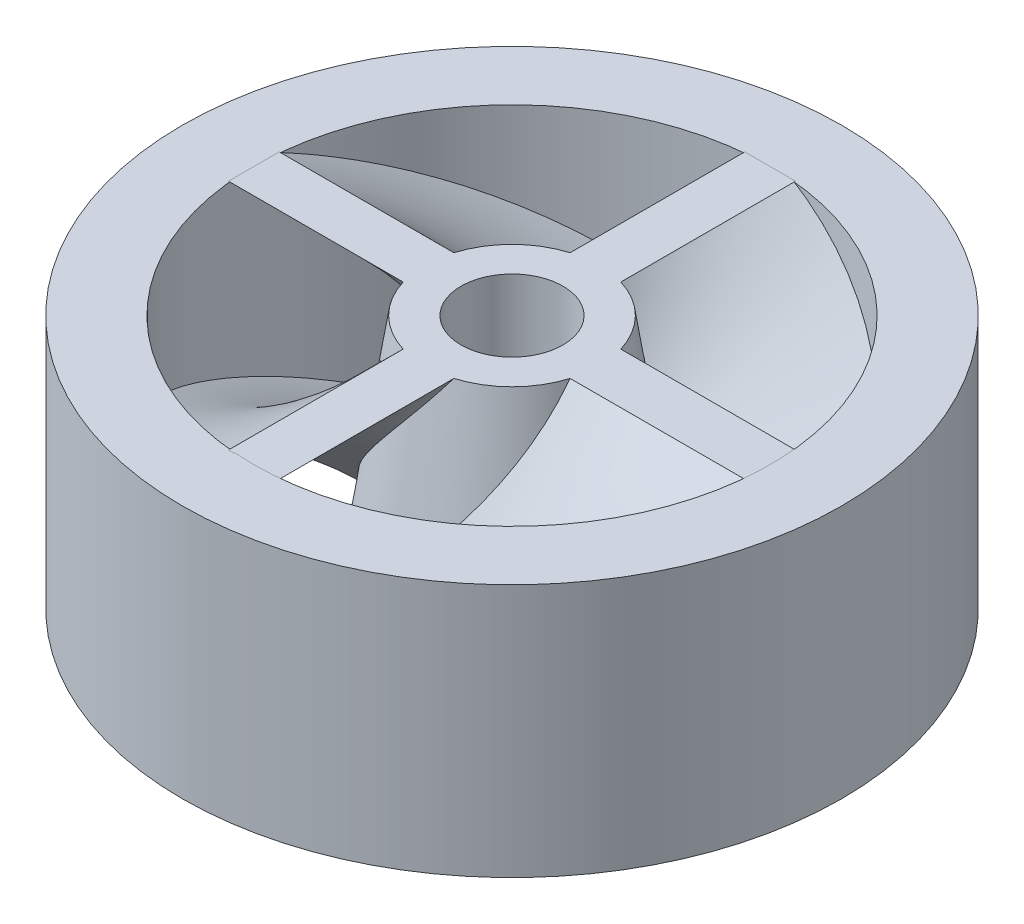
SolidWorks part; units mm, degrees
material "6061-T6 (SS)"
ref_plane "Front Plane" through (0, 0, 0) normal (0, 0, 1) x (1, 0, 0)
ref_plane "Top Plane" through (0, 0, 0) normal (0, 1, 0) x (1, 0, 0)
ref_plane "Right Plane" through (0, 0, 0) normal (1, 0, 0) x (0, 0, -1)
ref_axis "Axis1" through (0, 28.9225, 0) along (0, -1, 0)
sketch "Sketch1" plane through (0, 0, 0) normal (0, 1, 0) x (1, 0, 0)
  circle A0 centre (0, 0) radius 12.9286
  dimension "D1" = 25.8572
curve "Helix/Spiral1" pitch 38.862 height 12.7 radius 12.9286 centre (0, 0, 0) axis (0, -1, 0) start towards (0, 0, 1)
sketch "Sketch2" plane through (0, 0, 0) normal (0, 1, 0) x (1, 0, 0)
  line L0 (-1.27, -12.9286) -> (1.27, -12.9286)
  line L1 (1.27, 0) -> (-1.27, 0)
  line L2 (1.27, 0) -> (1.27, -12.9286)
  line L4 (-1.27, 0) -> (-1.27, -12.9286)
  point P4 (0, -12.9286)
  dimension "D2" = 2.54
  dimension "D1" = 12.9286
sweep "Sweep1" add profiles "Sketch2" path "Helix/Spiral1"
sketch "Sketch4" plane through (0, 0, 0) normal (0, 0, 1) x (1, 0, 0)
  line L0 (0, 0) -> (0, -12.7002)
  line L1 (0, 0) -> (4.3688, 0)
  line L2 (4.3688, 0) -> (6.35, -12.7002)
  line L3 (0, -12.7002) -> (-4.9832, -12.7002) construction
  line L4 (0, -12.7002) -> (6.35, -12.7002)
  spline S0 degree 1 poles (0.5892, -12.7) (-0.5892, -12.7004) knots 0 0 1 1 construction
  dimension "D1" = 4.3688
  dimension "D2" = 6.35
revolve "Revolve1" add sketch "Sketch4" angle 360 about L0
pattern_circular "CirPattern1" count 4 over 360 about axis through (0, 28.9225, 0) along (0, -1, 0) of "Sweep1"
hole_wizard "#10 Clearance Hole1" positions "3DSketch2" profile "Sketch9" hole size "#10" standard "ANSI Inch" end condition through all
sketch3d "3DSketch2"
  point P0 (0, 0, 0)
sketch "Sketch9" plane through (0, 0, 0) normal (1, 0, 0) x (0, 0, 1)
  line L0 (0, 0) -> (0, 12.7574)
  line L1 (0, 12.7574) -> (2.5527, 12.7574)
  line L2 (2.5527, 12.7574) -> (2.5527, 0)
  line L5 (2.5527, 0) -> (0, 0)
  line L11 (0, -6.35) -> (0, 107.95) construction
  dimension "Thru Hole Dia." = 5.1054
  dimension "Thru Hole Depth" = 12.7574
sketch "Sketch11" plane through (0, 0, 0) normal (0, 0, 1) x (1, 0, 0)
  line L1 (12.9286, 0) -> (16.51, 0)
  line L2 (12.9286, 0) -> (12.9286, -12.7)
  line L3 (12.9286, -12.7) -> (16.51, -12.7)
  line L4 (16.51, 0) -> (16.51, -12.7)
  line L6 (16.51, 0) -> (16.51, 6.1214)
  dimension "D1" = 12.7
  dimension "D2" = 12.9286
  dimension "D3" = 16.51
revolve "Revolve2" add sketch "Sketch11" angle 360 about axis through (0, 28.9225, 0) along (0, -1, 0) region at (14.7193, -6.35, 0)
equation "\"Height\"= 1 / 2"
equation "\"Tip Radius\"= .509"
equation "\"Hub Base Radius\"= .25"
equation "\"Blade Lead\"= 1.53"
equation "\"Axial Clearance\"= .381"
equation "\"D1@Sketch1\"= 2 * \"Tip Radius\""
equation "\"D1@Sketch2\"=\"Tip Radius\""
equation "\"D1@Sketch11\"=\"Height\""
equation "\"D2@Sketch11\"=\"Tip Radius\""
equation "\"Hub Top Radius\"=0.172"
equation "\"D1@Sketch4\"=\"Hub Top Radius\""
equation "\"D3@Sketch11\"= \"Inducer OD@[TP] [Pump] [Ox] Pump.Assembly\" / 2"
